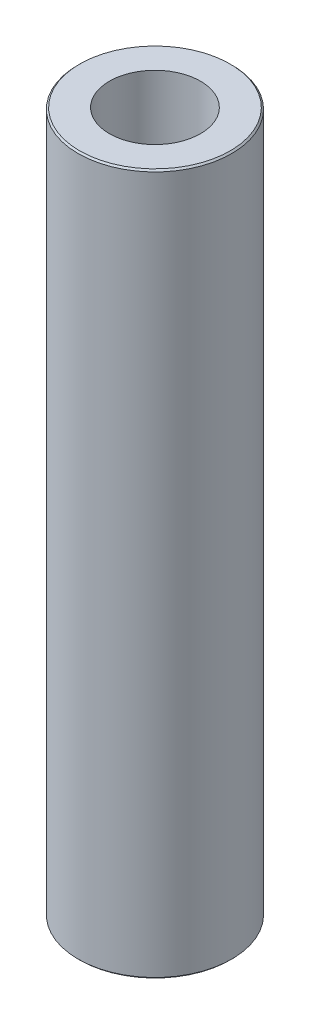
SolidWorks part; units mm, degrees
ref_plane "Front Plane" through (0, 0, 0) normal (0, 0, 1) x (1, 0, 0)
ref_plane "Top Plane" through (0, 0, 0) normal (0, 1, 0) x (1, 0, 0)
ref_plane "Right Plane" through (0, 0, 0) normal (1, 0, 0) x (0, 0, -1)
sketch "Sketch1" plane through (0, 0, 0) normal (0, 1, 0) x (1, 0, 0)
  circle A0 centre (0, 0) radius 15
  dimension "SHAFT_OD" = 30
extrude "Boss-Extrude1" add sketch "Sketch1" along normal blind 136.8448
sketch "Sketch2" plane through (0, 0, 0) normal (0, 1, 0) x (1, 0, 0)
  circle A0 centre (0, 0) radius 8.8937
  dimension "BORE_D" = 17.7874
extrude "Cut-Extrude1" cut sketch "Sketch2" along normal through all
chamfer "Chamfer1" distance 0.3065 angle 45 2 edges at (0, 136.8448, 15) (0, 0, 15)
